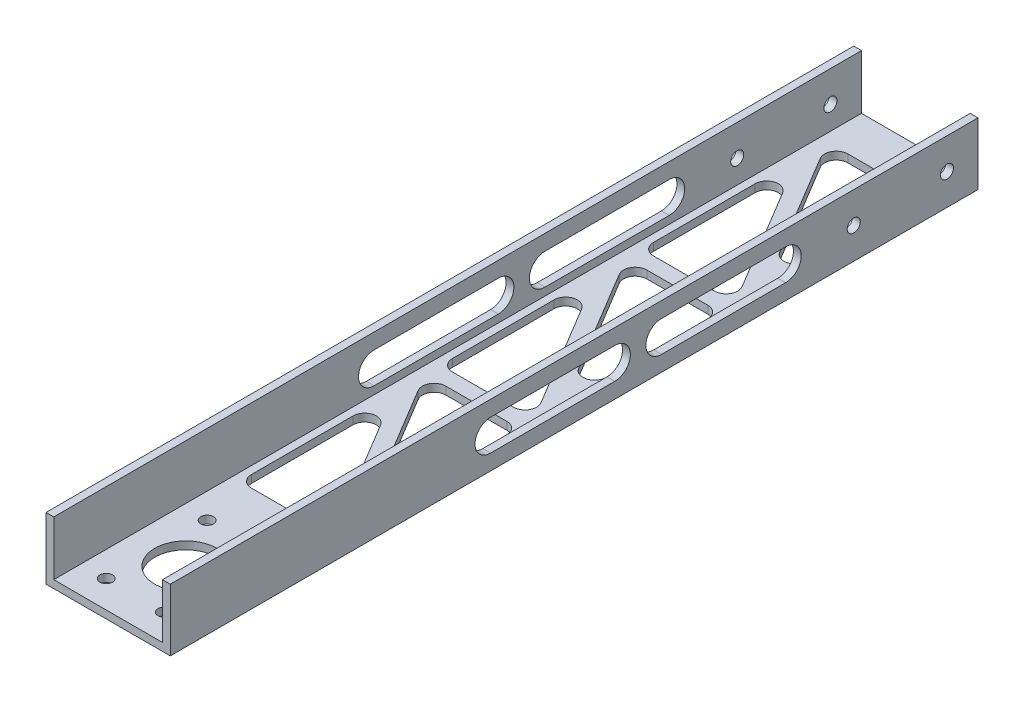
SolidWorks part; units mm, degrees
material "6063-T6"
ref_plane "Front" through (0, 0, 0) normal (0, 0, 1) x (1, 0, 0)
ref_plane "Top" through (0, 0, 0) normal (0, 1, 0) x (1, 0, 0)
ref_plane "Right" through (0, 0, 0) normal (1, 0, 0) x (0, 0, -1)
sketch "Sketch1" plane through (0, 0, 0) normal (0, 0, 1) x (1, 0, 0)
  line L0 (47.625, 3.175) -> (47.625, 25.4)
  line L1 (0, 0) -> (50.8, 0)
  line L2 (0, 0) -> (0, 25.4)
  line L4 (50.8, 0) -> (50.8, 25.4)
  line L5 (3.175, 3.175) -> (47.625, 3.175)
  line L6 (3.175, 3.175) -> (3.175, 25.4)
  line L7 (50.8, 25.4) -> (47.625, 25.4)
  line L8 (0, 25.4) -> (3.175, 25.4)
  dimension "D1" = 25.4
  dimension "D2" = 50.8
  dimension "D3" = 3.175
extrude "Boss-Extrude1" add sketch "Sketch1" along normal blind 330.2
sketch "Sketch2" plane through (0, 0, 0) normal (0, -1, 0) x (1, 0, 0)
  line L0 (25.4, 298.45) -> (25.4, 330.2) construction
  line L1 (0, 330.2) -> (50.8, 330.2) construction
  circle A0 centre (25.4, 298.45) radius 12.7
  dimension "D1" = 25.4
  dimension "D2" = 31.75
extrude "Cut-Extrude1" cut sketch "Sketch2" against normal up to next
sketch "Sketch3" plane through (50.8, 0, 0) normal (1, 0, 0) x (0, 0, -1)
  line L0 (-12.7, 12.7) -> (0, 12.7) construction
  line L1 (0, 0) -> (0, 25.4) construction
  line L2 (-12.7, 12.7) -> (-50.8, 12.7) construction
  circle A0 centre (-12.7, 12.7) radius 2.667
  circle A1 centre (-50.8, 12.7) radius 2.667
  dimension "D1" = 5.334
  dimension "D4" = 5.334
  dimension "D2" = 12.7
  dimension "D3" = 38.1
extrude "Cut-Extrude2" cut sketch "Sketch3" against normal through all
sketch "Sketch4" plane through (0, 0, 0) normal (0, -1, 0) x (1, 0, 0)
  circle A1 centre (13.4937, 277.8278) radius 2.5908
  circle A3 centre (37.3062, 277.8278) radius 2.5908
  circle A5 centre (13.4937, 319.0722) radius 2.5908
  circle A7 centre (37.3062, 319.0722) radius 2.5908
extrude "Cut-Extrude3" cut sketch "Sketch4" against normal up to next
sketch "Sketch5" plane through (0, 0, 0) normal (0, -1, 0) x (1, 0, 0)
  line L8 (0, 330.2) -> (0, 0) construction
  line B0 (40.1223, 85.7734) -> (15.1963, 44.23)
  line B1 (6.35, 40.4053) -> (0, 40.4053) construction
  line B2 (14.7615, 17.144) -> (39.6875, 17.144)
  line B3 (6.35, 17.144) -> (6.35, 80.644) construction
  line B4 (6.35, 80.644) -> (44.45, 80.644) construction
  line B5 (44.45, 21.9065) -> (44.45, 63.4499)
  line B6 (10.6777, 24.3568) -> (35.6037, 65.9001)
  line B7 (6.35, 80.644) -> (44.45, 17.144) construction
  line B8 (44.45, 37.6448) -> (50.8, 37.6448) construction
  arc B9 (35.6037, 65.9001) -> (44.45, 63.4499) centre (39.6875, 63.4499) cw
  arc B10 (39.6875, 17.144) -> (44.45, 21.9065) centre (39.6875, 21.9065) ccw
  arc B11 (10.6777, 24.3568) -> (14.7615, 17.144) centre (14.7615, 21.9065) ccw
  line B12 (36.0385, 92.9862) -> (11.1125, 92.9862)
  arc B13 (40.1223, 85.7734) -> (36.0385, 92.9862) centre (36.0385, 88.2237) ccw
  arc B14 (11.1125, 92.9862) -> (6.35, 88.2237) centre (11.1125, 88.2237) ccw
  line B15 (6.35, 88.2237) -> (6.35, 46.6803)
  arc B16 (15.1963, 44.23) -> (6.35, 46.6803) centre (11.1125, 46.6803) cw
  line B17 (40.1223, 167.9656) -> (15.1963, 126.4222)
  line B18 (14.7615, 99.3362) -> (39.6875, 99.3362)
  line B19 (44.45, 104.0987) -> (44.45, 145.642)
  line B20 (10.6777, 106.549) -> (35.6037, 148.0923)
  arc B21 (35.6037, 148.0923) -> (44.45, 145.642) centre (39.6875, 145.642) cw
  arc B22 (39.6875, 99.3362) -> (44.45, 104.0987) centre (39.6875, 104.0987) ccw
  arc B23 (10.6777, 106.549) -> (14.7615, 99.3362) centre (14.7615, 104.0987) ccw
  line B24 (36.0385, 175.1784) -> (11.1125, 175.1784)
  arc B25 (40.1223, 167.9656) -> (36.0385, 175.1784) centre (36.0385, 170.4159) ccw
  arc B26 (11.1125, 175.1784) -> (6.35, 170.4159) centre (11.1125, 170.4159) ccw
  line B27 (6.35, 170.4159) -> (6.35, 128.8725)
  arc B28 (15.1963, 126.4222) -> (6.35, 128.8725) centre (11.1125, 128.8725) cw
  line B29 (40.1223, 250.1577) -> (15.1963, 208.6144)
  line B30 (14.7615, 181.5284) -> (39.6875, 181.5284)
  line B31 (44.45, 186.2909) -> (44.45, 227.8342)
  line B32 (10.6777, 188.7411) -> (35.6037, 230.2845)
  arc B33 (35.6037, 230.2845) -> (44.45, 227.8342) centre (39.6875, 227.8342) cw
  arc B34 (39.6875, 181.5284) -> (44.45, 186.2909) centre (39.6875, 186.2909) ccw
  arc B35 (10.6777, 188.7411) -> (14.7615, 181.5284) centre (14.7615, 186.2909) ccw
  line B36 (36.0385, 257.3705) -> (11.1125, 257.3705)
  arc B37 (40.1223, 250.1577) -> (36.0385, 257.3705) centre (36.0385, 252.608) ccw
  arc B38 (11.1125, 257.3705) -> (6.35, 252.608) centre (11.1125, 252.608) ccw
  line B39 (6.35, 252.608) -> (6.35, 211.0647)
  arc B40 (15.1963, 208.6144) -> (6.35, 211.0647) centre (11.1125, 211.0647) cw
  dimension "D1" = 6.35
  dimension "D2" = 6.35
sketch_block_instance "Block2-1"
sketch_block "Block2" parameters "D1"=6.35
sketch_block_instance "Block1-4"
sketch_block "Block1" parameters "D3"=4.7625, "D1"=63.5, "D2"=38.1
sketch_block_instance "Block1-1"
sketch_block_instance "Block2-2"
sketch_block_instance "Block2-4"
extrude "Cut-Extrude4" cut sketch "Sketch5" against normal up to next
sketch "Sketch6" plane through (0, 0, 0) normal (-1, 0, 0) x (0, 0, 1)
  line L0 (78.617, 12.7) -> (129.417, 12.7) construction
  line L1 (78.617, 19.05) -> (129.417, 19.05)
  line L2 (78.617, 6.35) -> (129.417, 6.35)
  line L3 (330.2, 25.4) -> (0, 25.4) construction
  line L4 (84.874, 19.05) -> (84.874, 25.4) construction
  line L5 (88.704, 6.35) -> (88.704, 0) construction
  line L6 (330.2, 0) -> (0, 0) construction
  line L7 (154.724, 19.05) -> (154.724, 25.4) construction
  line L8 (158.554, 6.35) -> (158.554, 0) construction
  line L9 (148.467, 12.7) -> (199.267, 12.7) construction
  line L10 (148.467, 19.05) -> (199.267, 19.05)
  line L11 (148.467, 6.35) -> (199.267, 6.35)
  arc A0 (78.617, 19.05) -> (78.617, 6.35) centre (78.617, 12.7) ccw
  arc A1 (129.417, 6.35) -> (129.417, 19.05) centre (129.417, 12.7) ccw
  arc A2 (148.467, 19.05) -> (148.467, 6.35) centre (148.467, 12.7) ccw
  arc A3 (199.267, 6.35) -> (199.267, 19.05) centre (199.267, 12.7) ccw
  point P2 (104.017, 12.7)
  point P18 (173.867, 12.7)
  dimension "D1" = 12.7
  dimension "D2" = 50.8
  dimension "D3" = 2
extrude "Cut-Extrude5" cut sketch "Sketch6" against normal through all
